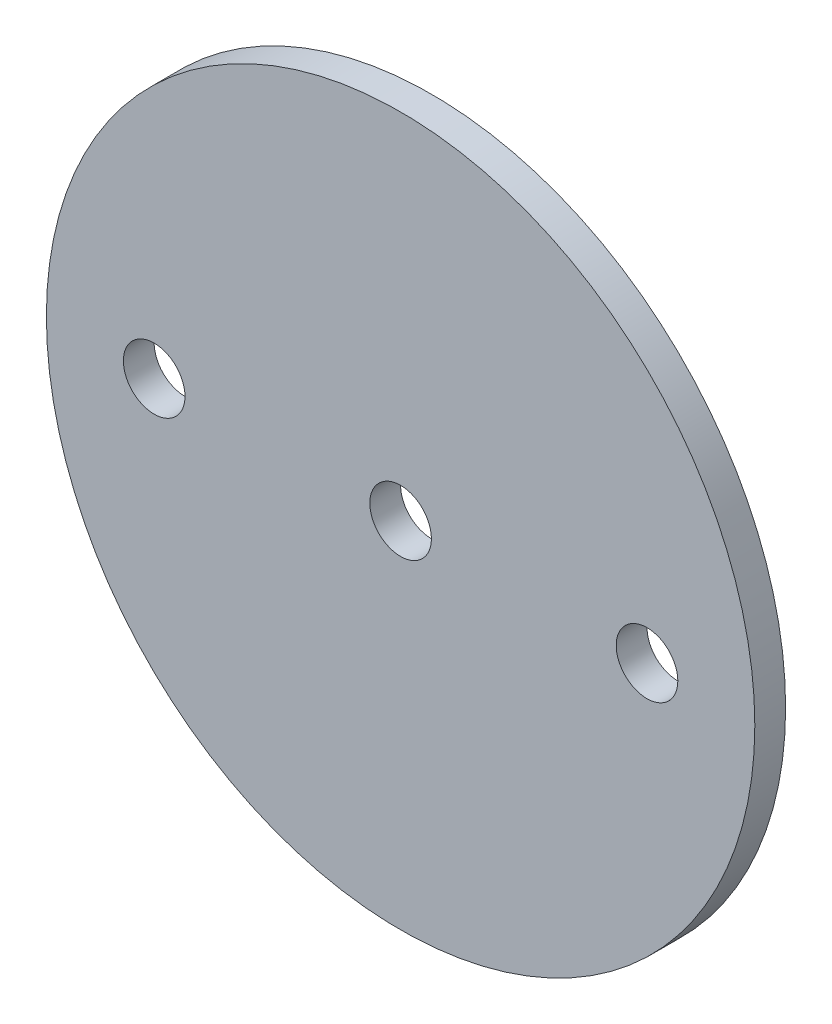
SolidWorks part; units mm, degrees
ref_plane "Front Plane" through (0, 0, 0) normal (0, 0, 1) x (1, 0, 0)
ref_plane "Top Plane" through (0, 0, 0) normal (0, 1, 0) x (1, 0, 0)
ref_plane "Right Plane" through (0, 0, 0) normal (1, 0, 0) x (0, 0, -1)
sketch "Sketch1" plane through (0, 0, 0) normal (0, 0, 1) x (1, 0, 0)
  circle A0 centre (0, 0) radius 36.5125
  dimension "D1" = 73.025
extrude "Boss-Extrude1" add sketch "Sketch1" along normal mid plane 3.175
sketch "Sketch2" plane through (0, 0, 1.5875) normal (0, 0, 1) x (1, 0, 0)
  line L0 (-1000, 0) -> (49000, 0) construction
  point P1 (0, 0)
  point P4 (25.4, 0)
  point P5 (-25.4, 0)
  dimension "D1" = 25.4
  dimension "D2" = 50.8
hole_wizard "1/4 (0.25) Diameter Hole1" positions "Sketch2" profile "Sketch3" hole size "1/4" standard "ANSI Inch" end condition through all
sketch "Sketch3" plane through (-25.4, 0, 1.5875) normal (1, 0, 0) x (0, -1, 0)
  line L0 (0, 0) -> (0, 3.175)
  line L1 (0, 3.175) -> (3.175, 3.175)
  line L2 (3.175, 3.175) -> (3.175, 0)
  line L5 (3.175, 0) -> (0, 0)
  line L11 (0, -6.35) -> (0, 107.95) construction
  dimension "Thru Hole Dia." = 6.35
  dimension "Thru Hole Depth" = 3.175
equation "\"AIRFRAME_OD\"= 3.091in"
equation "\"AIRFRAME_ID\"= 3.00in"
equation "\"FLAT_T\"= 0.125in"
equation "\"NOSE_EXP_L\"= 3.5in"
equation "\"NOSE_SHOULDER_L\"= 5in"
equation "\"MAIN_L\"= 30in"
equation "\"RECO_COUP_L\"= 6in"
equation "\"RECO_SWITCH_L\"= 1.5in"
equation "\"DROGUE_L\"= 14in"
equation "\"ATS_FORE_COUP_L\"= 4in"
equation "\"ATS_AFT_COUP_L\"= 2.5in"
equation "\"LOWER_L\"= 16in"
equation "\"FIN_N\"= 4"
equation "\"CR_AFT_X\"= 0.5in"
equation "\"CR_FORE_X\"= 6in"
equation "\"FIN_ROOT\"= 5in"
equation "\"FIN_X\"= 0.75in"
equation "\"MOTOR_OD\"= 2.25in"
equation "\"MOTOR_ID\"= 2.126in"
equation "\"COUPLER_OD\"= 2.998in"
equation "\"COUPLER_ID\"= 2.875in"
equation "\"D1@Sketch1\"=\"COUPLER_ID\""
equation "\"D1@Boss-Extrude1\"=\"FLAT_T\""
equation "\"RECO_ROD_X\"= 1.5in"
equation "\"ATS_ROD_X\"= 2in"
equation "\"D1@Sketch2\"=\"ATS_ROD_X\"*0.5"
equation "\"D2@Sketch2\"=\"ATS_ROD_X\""
